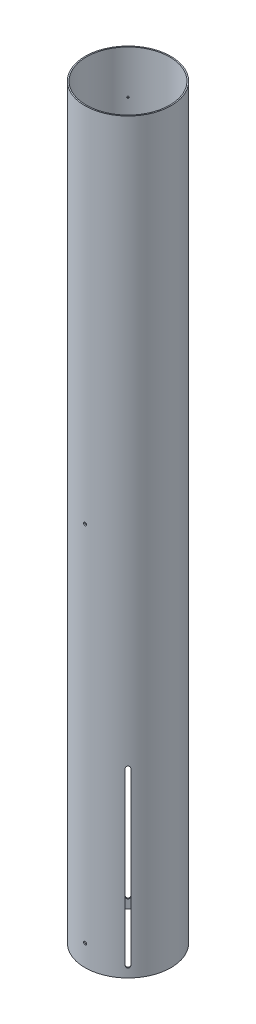
SolidWorks part; units mm, degrees
material "Wildman Fiberglass"
ref_plane "Front Plane" through (0, 0, 0) normal (0, 0, 1) x (1, 0, 0)
ref_plane "Top Plane" through (0, 0, 0) normal (0, 1, 0) x (1, 0, 0)
ref_plane "Right Plane" through (0, 0, 0) normal (1, 0, 0) x (0, 0, -1)
sketch "Sketch1" plane through (0, 0, 0) normal (0, 1, 0) x (1, 0, 0)
  circle A0 centre (0, 0) radius 49.657
  circle A1 centre (0, 0) radius 51.054
  dimension "D1" = 102.108
  dimension "D2" = 99.314
extrude "Boss-Extrude1" add sketch "Sketch1" along normal blind 887.984
extrude "Cut-Extrude1" cut sketch "Sketch2" against normal blind 152.4
sketch "Sketch2" plane through (14.4921, 1243.3556, -192.6285) normal (0.7071, 0, -0.7071) x (0, 1, 0)
  line L0 (-1230.6556, 128.3427) -> (-1027.4556, 128.3427)
  line L1 (-1027.4556, 123.5802) -> (-1230.6556, 123.5802)
  arc A0 (-1230.6556, 128.3427) -> (-1230.6556, 123.5802) centre (-1230.6556, 125.9615) ccw
  arc A1 (-1027.4556, 128.3427) -> (-1027.4556, 123.5802) centre (-1027.4556, 125.9615) cw
pattern_circular "CirPattern1" count 4 over 360 about axis through (0, 887.984, 0) along (0, -1, 0) of "Cut-Extrude1" reverse direction yes
extrude "Cut-Extrude2" cut sketch "Sketch3" against normal blind 11.684
sketch "Sketch3" plane through (271.0916, 1243.3556, 52.6415) normal (0, 0, 1) x (-1, 0, 0)
  circle A0 centre (271.0916, 1217.9556) radius 1.7653
  circle A2 centre (271.0916, 786.1556) radius 1.7653
extrude "Cut-Extrude3" cut sketch "Sketch4" against normal blind 25.4
sketch "Sketch4" plane through (120.5803, 706.3726, -48.7382) normal (0.7071, 0, 0.7071) x (-0.7071, 0, 0.7071)
  line L0 (68.6723, -129.7954) -> (170.7803, -129.7954) construction
  circle A0 centre (119.7263, -129.7954) radius 1.0922
pattern_circular "CirPattern2" count 2 over 360 about axis through (0, 887.984, 0) along (0, -1, 0) of "Cut-Extrude3"
equation "\"Length\"=34.96"
equation "\"D1@Boss-Extrude1\"=\"Length\""
